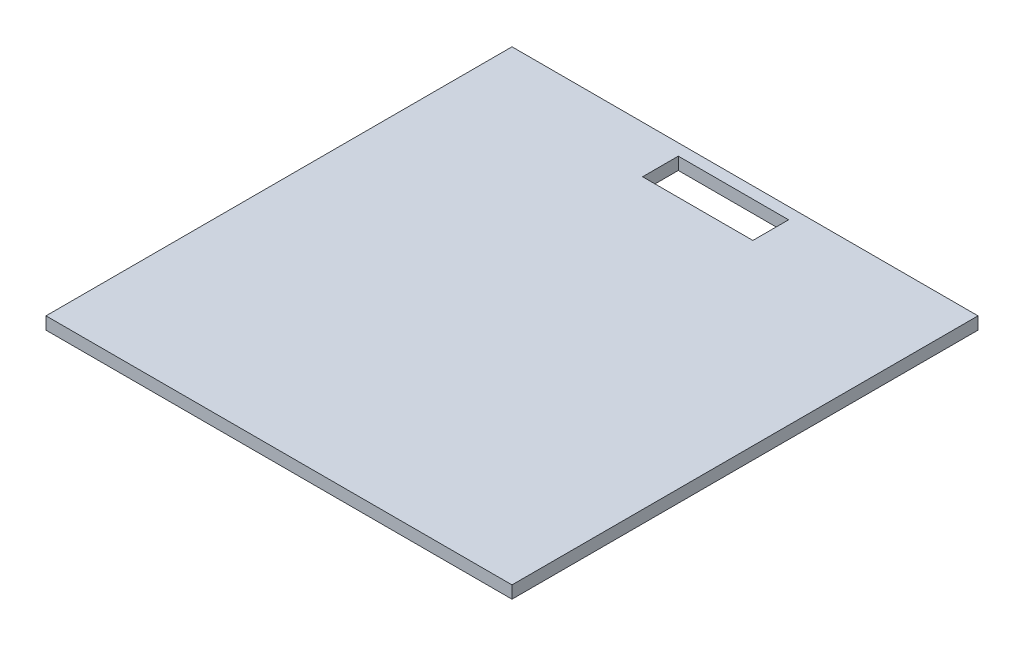
SolidWorks part; units mm, degrees
material "ABS PC"
ref_plane "Front Plane" through (0, 0, 0) normal (0, 0, 1) x (1, 0, 0)
ref_plane "Top Plane" through (0, 0, 0) normal (0, 1, 0) x (1, 0, 0)
ref_plane "Right Plane" through (0, 0, 0) normal (1, 0, 0) x (0, 0, -1)
sketch "Sketch1" plane through (0, 0, 0) normal (0, 1, 0) x (1, 0, 0)
  line L1 (-150, 150) -> (150, 150)
  line L2 (-150, 150) -> (-150, -150)
  line L3 (-150, -150) -> (150, -150)
  line L4 (150, 150) -> (150, -150)
  line L5 (-150, 150) -> (150, -150) construction
  line L6 (-150, -150) -> (150, 150) construction
  line L11 (-35.5, 142.5658) -> (35.5, 142.5658)
  line L12 (-35.5, 142.5658) -> (-35.5, 119.5658)
  line L13 (-35.5, 119.5658) -> (35.5, 119.5658)
  line L14 (35.5, 142.5658) -> (35.5, 119.5658)
  line L15 (-35.5, 142.5658) -> (35.5, 119.5658) construction
  line L16 (-35.5, 119.5658) -> (35.5, 142.5658) construction
  point P0 (0, 0)
  point P6 (0, 131.0658)
  dimension "D1" = 300
  dimension "D2" = 300
  dimension "D3" = 71
  dimension "D4" = 23
extrude "Boss-Extrude1" add sketch "Sketch1" along normal blind 0.2
extrude "Boss-Extrude2" add sketch "Sketch1<3>" along normal blind 8
sketch "Sketch1<3>" plane through (0, 0, 0) normal (0, 1, 0) x (1, 0, 0) same geometry as "Sketch1"
